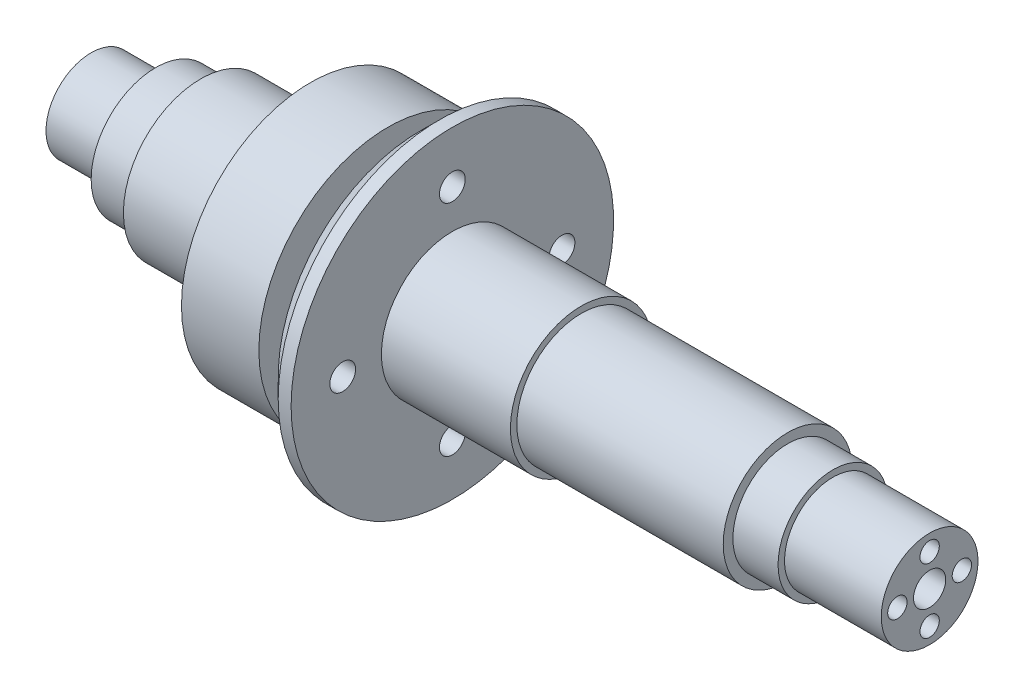
SolidWorks part; units mm, degrees
material "2024-T4"
ref_plane "Front Plane" through (0, 0, 0) normal (0, 0, 1) x (1, 0, 0)
ref_plane "Top Plane" through (0, 0, 0) normal (0, 1, 0) x (1, 0, 0)
ref_plane "Right Plane" through (0, 0, 0) normal (1, 0, 0) x (0, 0, -1)
other "Center of Mass"
sketch "Sketch3" plane through (0, 0, 0) normal (0, 0, 1) x (1, 0, 0)
  line L0 (0, 0) -> (0, 39.0464) construction
  line L1 (-72.5, 0) -> (72.5, 0) construction
  line L2 (-72.5, 2.5) -> (-72.5, 0) construction
  line L3 (-72.5, 2.5) -> (-72.5, 7)
  line L4 (-72.5, 7) -> (-62.5, 7)
  line L5 (-62.5, 7) -> (-62.5, 10)
  line L6 (-62.5, 10) -> (-55.5, 10)
  line L7 (-55.5, 10) -> (-55.5, 12)
  line L8 (-55.5, 12) -> (-38.5, 12)
  line L9 (-38.5, 12) -> (-38.5, 20)
  line L10 (-38.5, 20) -> (-26.5, 20)
  line L11 (-26.5, 20) -> (-26.5, 11)
  line L12 (-26.5, 11) -> (-21.5, 11)
  line L13 (3.5, 11) -> (3.5, 10)
  line L14 (3.5, 10) -> (35.5, 10)
  line L15 (35.5, 10) -> (35.5, 8.5)
  line L17 (72.5, 7.5) -> (72.5, 2.5)
  line L18 (72.5, 2.5) -> (-72.5, 2.5)
  line L19 (-32.5, 20) -> (-32.5, 2.5) construction
  line L20 (-11.5, 11) -> (-11.5, 2.5) construction
  line L21 (-77.5, 12) -> (-72.8417, 12) construction
  line L22 (-62.5, 10) -> (-62.5, 16) construction
  line L23 (-77.5, 15) -> (-72.8417, 15) construction
  line L24 (35.5, 8.5) -> (42.5, 8.5)
  line L25 (11.9511, 11) -> (20.8732, 11) construction
  line L26 (30.861, 12) -> (33.3773, 12) construction
  line L27 (42.5, 8.5) -> (42.5, 7.5)
  line L36 (42.5, 7.5) -> (72.5, 7.5)
  line L37 (-21.5, 11) -> (-21.5, 25)
  line L38 (35.5, 8.5) -> (44.5, 8.5) construction
  line L39 (-21.5, 25) -> (-16.5, 25)
  line L40 (-16.5, 25) -> (-16.5, 11)
  line L42 (-16.5, 11) -> (3.5, 11)
  point P5 (0, 0)
  dimension "D3" = 40
  dimension "D2" = 22
  dimension "D4" = 40
  dimension "D5" = 12
  dimension "D6" = 10
  dimension "D7" = 7
  dimension "D9" = 5
  dimension "D10" = 14
  dimension "D11" = 20
  dimension "D12" = 12
  dimension "D13" = 24
  dimension "D14" = 32
  dimension "D15" = 15
  dimension "D16" = 20
  dimension "D18" = 11
  dimension "D20" = 12
  dimension "D21" = 7
  dimension "D22" = 17
  dimension "D24" = 15
  dimension "D8" = 30
  dimension "D17" = 32
  dimension "D19" = 30
  dimension "D23" = 5
  dimension "D25" = 5
  dimension "D26" = 25
revolve "Revolve1" add sketch "Sketch3" angle 360 about L1
ref_plane "Plane1" through (0, 11, 0) normal (0, 1, 0) x (1, 0, 0)
sketch "Sketch4" plane through (0, 11, 0) normal (0, 1, 0) x (1, 0, 0)
  line L0 (3.5, 0) -> (-26.5, 0) construction
  line L1 (3.5, -11) -> (3.5, 11) construction
  line L2 (-26.5, -11) -> (-26.5, 11) construction
  line L3 (-11.5, 0) -> (-11.5, 23.5234) construction
  line L4 (72.5, -7.5) -> (72.5, 7.5) construction
  line L5 (72.5, 0) -> (62.5, 0) construction
  line L6 (-17.5, -2) -> (-5.5, -2)
  line L7 (-17.5, -2) -> (-17.5, 2)
  line L8 (-17.5, 2) -> (-5.5, 2)
  line L9 (-5.5, -2) -> (-5.5, 2)
  line L10 (-17.5, -2) -> (-5.5, 2) construction
  line L11 (-17.5, 2) -> (-5.5, -2) construction
  line L16 (56.5, -2) -> (68.5, -2)
  line L17 (56.5, -2) -> (56.5, 2)
  line L18 (56.5, 2) -> (68.5, 2)
  line L19 (68.5, -2) -> (68.5, 2)
  line L20 (56.5, -2) -> (68.5, 2) construction
  line L21 (56.5, 2) -> (68.5, -2) construction
  point P17 (62.5, 0)
  dimension "D1" = 12
  dimension "D2" = 4
  dimension "D3" = 10
  dimension "D4" = 12
  dimension "D5" = 4
fillet "Fillet1" radius 1 2 edges at (-26.5, 0, 11) (-38.5, 0, 12)
ref_plane "Plane2" through (0, 7.5, 0) normal (0, 1, 0) x (1, 0, 0)
sketch "Sketch5" plane through (0, 7.5, 0) normal (0, 1, 0) x (1, 0, 0)
  line L0 (68.5, -2) -> (68.5, 2) construction
  line L1 (56.5, -2) -> (68.5, -2) construction
  line L2 (56.5, -2) -> (56.5, 2) construction
  line L3 (56.5, 2) -> (68.5, 2) construction
  line L4 (68.5, -2) -> (68.5, 2)
  line L5 (56.5, -2) -> (68.5, -2)
  line L6 (56.5, -2) -> (56.5, 2)
  line L7 (56.5, 2) -> (68.5, 2)
sketch "Sketch6" [suppressed] plane through (0, 0, 0) normal (0, 0, 1) x (1, 0, 0)
  line L0 (-52.75, 0) -> (52.75, 0) construction
  line L1 (-52.75, 5.5) -> (-52.75, 7)
  line L2 (-52.75, 7) -> (-42.75, 7)
  line L3 (-42.75, 7) -> (-42.75, 10)
  line L4 (-42.75, 10) -> (-35.75, 10)
  line L5 (-35.75, 10) -> (-35.75, 12)
  line L6 (-35.75, 12) -> (-28.25, 12)
  line L7 (-28.25, 12) -> (-28.25, 11)
  line L8 (-28.25, 11) -> (-1.75, 11)
  line L9 (44.75, 11) -> (44.75, 8.5)
  line L10 (44.75, 8.5) -> (52.75, 8.5)
  line L11 (52.75, 8.5) -> (52.75, 5.5)
  line L12 (52.75, 5.5) -> (-52.75, 5.5)
  line L13 (8.25, 11) -> (8.25, 5.5) construction
  line L14 (-1.75, 11) -> (-1.75, 22)
  line L15 (-1.75, 22) -> (3.25, 22)
  line L16 (3.25, 22) -> (3.25, 11)
  line L17 (3.25, 11) -> (44.75, 11)
  point P4 (0, 0)
  dimension "D1" = 10
  dimension "D2" = 7
  dimension "D3" = 8
  dimension "D4" = 61
  dimension "D5" = 105.5
  dimension "D6" = 7
  dimension "D7" = 10
  dimension "D8" = 12
  dimension "D9" = 11
  dimension "D10" = 8.5
  dimension "D11" = 11
  dimension "D12" = 31.5
  dimension "D13" = 5
  dimension "D14" = 22
  dimension "D15" = 24.5
revolve "Revolve2" [suppressed] add sketch "Sketch6" angle 360 about L0
ref_plane "Plane3" [suppressed] through (0, 11, 0) normal (0, 1, 0) x (1, 0, 0)
sketch "Sketch8" plane through (-16.5, 0, 0) normal (1, 0, 0) x (0, 0, -1)
  line L0 (0, 0) -> (0, 17) construction
  circle A0 centre (0, 17) radius 2
  circle A1 centre (17, 0) radius 2
  circle A2 centre (0, -17) radius 2
  circle A3 centre (-17, 0) radius 2
  point P12 (0, 0)
  dimension "D1" = 4
  dimension "D3" = 17
  dimension "D4" = 17
  dimension "D5" = 34
  dimension "D2" = 4
extrude "Cut-Extrude5" cut sketch "Sketch8" against normal up to surface (5 mm away) up to face at (-21.5, 0, 11)
sketch "Sketch9" [suppressed] plane through (3.25, 0, 0) normal (1, 0, 0) x (0, 0, -1)
  line L0 (0, 0) -> (0, 17) construction
  circle A0 centre (0, 17) radius 2
  circle A1 centre (17, 0) radius 2
  circle A2 centre (0, -17) radius 2
  circle A3 centre (-17, 0) radius 2
  point P12 (0, 0)
  dimension "D1" = 4
  dimension "D2" = 17
  dimension "D4" = 17
  dimension "D5" = 17
  dimension "D3" = 4
extrude "Cut-Extrude6" [suppressed] cut sketch "Sketch9" against normal up to surface (5 mm away)
sketch "Sketch10" plane through (72.5, 0, 0) normal (1, 0, 0) x (0, 0, -1)
  circle A1 centre (0, 0) radius 7.5 construction
  circle A2 centre (0, 0) radius 7.5
extrude "Cut-Extrude7" cut sketch "Sketch10" against normal blind 15
sketch "Sketch11" plane through (57.5, 0, 0) normal (1, 0, 0) x (0, 0, -1)
  line L0 (0, 0) -> (0, 5) construction
  circle A0 centre (0, 5) radius 1.5
  circle A1 centre (5, 0) radius 1.5
  circle A2 centre (0, -5) radius 1.5
  circle A3 centre (-5, 0) radius 1.5
  point P12 (0, 0)
  dimension "D1" = 3
  dimension "D3" = 5
  dimension "D2" = 4
extrude "Cut-Extrude8" cut sketch "Sketch11" against normal blind 10
chamfer "Chamfer1" distance 3 angle 45 1 edges at (-21.5, 0, 25)
equation "\"mainShaft-D\"= 20mm"
equation "\"mainTrackGear-D\"= 40mm"
equation "\"D4@Sketch3\"=\"wormGearL-D\""
equation "\"D11@Sketch3\"=\"mainShaft-D\""
equation "\"mini-flipper-shaft-diameter\"= 26mm"
equation "\"mini-shaft-ring-groove-diam\"= 7.8mm"
equation "\"mini-shaft-ring-groove-width\"= 1mm"
equation "\"dtCoverPlate-DistFrom-GearCent\"= 73mm"
equation "\"wormGearShaft-L\"= \"dtCoverPlate-DistFrom-GearCent\" - 27.75 + 3.75"
equation "\"wormGearShaft-Dsmall\"= 6mm"
equation "\"wormGearShaft-Dworm\"= 12mm"
equation "\"wormL-D\" = 12mm"
equation "\"wormR-D\" = 15mm"
equation "\"wormGearL-D\" = 40mm"
equation "\"wormGearR-D\" = 50mm"
